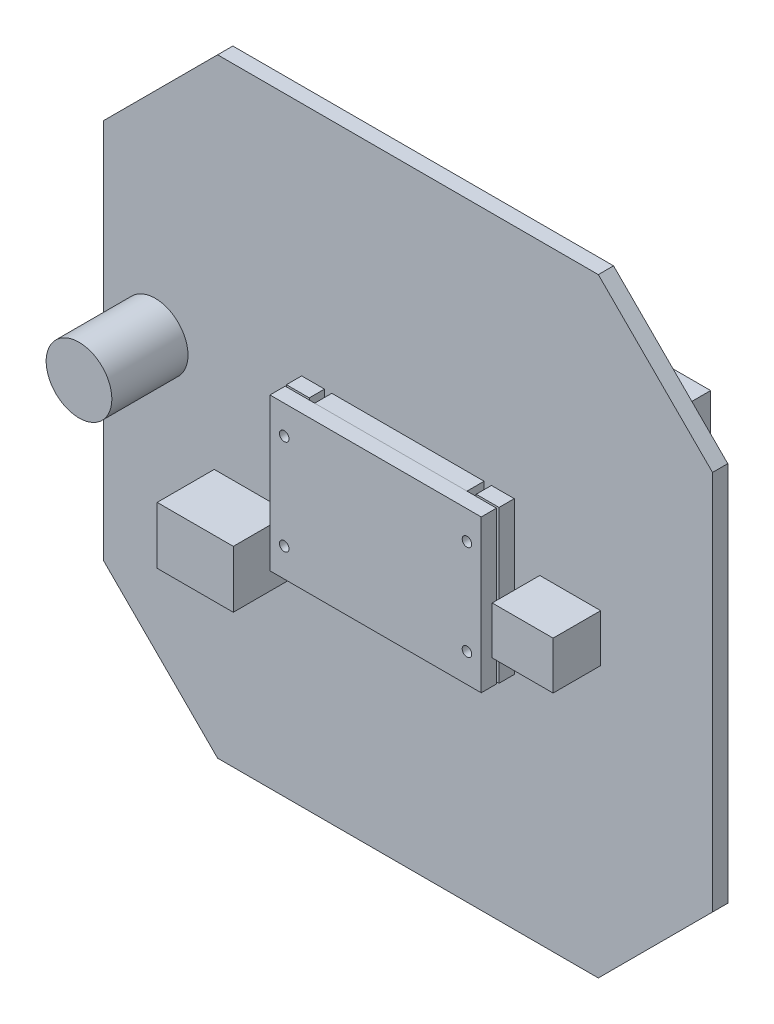
SolidWorks part; units mm, degrees
ref_plane "Front Plane" through (0, 0, 0) normal (0, 0, 1) x (1, 0, 0)
ref_plane "Top Plane" through (0, 0, 0) normal (0, 1, 0) x (1, 0, 0)
ref_plane "Right Plane" through (0, 0, 0) normal (1, 0, 0) x (0, 0, -1)
ref_plane "Plane1" through (0, -0.4, 0) normal (0, 1, 0) x (1, 0, 0)
ref_axis "FPGA Center" through (0, -0.4, 56.35) along (0, 0, -1)
ref_axis "Board Center" through (0, 0, -2.335) along (0, 0, 1)
sketch "Sketch1" plane through (0, 0, 0) normal (0, 0, 1) x (1, 0, 0)
  line L0 (-10, 16) -> (-16, 10)
  line L1 (-10, 16) -> (10, 16)
  line L2 (-16, 10) -> (-16, -10)
  line L3 (-10, -16) -> (10, -16)
  line L4 (16, 10) -> (16, -10)
  line L5 (-16, 16) -> (16, -16) construction
  line L6 (-16, -16) -> (16, 16) construction
  line L7 (10, 16) -> (16, 10)
  line L8 (16, -10) -> (10, -16)
  line L9 (-16, -10) -> (-10, -16)
  circle A0 centre (0, 0) radius 20 construction
  dimension "D1" = 40
  dimension "D2" = 32
  dimension "D3" = 32
extrude "Boss-Extrude1" add sketch "Sketch1" along normal blind 0.8
sketch "Sketch2" plane through (0, 0, 0) normal (0, 0, -1) x (-1, 0, 0)
  line L1 (5.2243, -14) -> (-11.7757, -14)
  line L2 (5.2243, -14) -> (5.2243, -11)
  line L3 (5.2243, -11) -> (-11.7757, -11)
  line L4 (-11.7757, -14) -> (-11.7757, -11)
  dimension "D1" = 3
  dimension "D2" = 17
  dimension "D3" = 11
  dimension "D4" = 5.2243
extrude "Boss-Extrude2" add sketch "Sketch2" along normal blind 1.5
sketch "Sketch3" plane through (0, 0, 0.8) normal (0, 0, 1) x (1, 0, 0)
  line L1 (-4, 3.6) -> (4, 3.6)
  line L2 (-4, 3.6) -> (-4, -4.4)
  line L3 (-4, -4.4) -> (4, -4.4)
  line L4 (4, 3.6) -> (4, -4.4)
  line L5 (-4, 3.6) -> (4, -4.4) construction
  line L6 (-4, -4.4) -> (4, 3.6) construction
  point P0 (3.0251, -6.0236)
  point P9 (0, -0.4)
  dimension "D1" = 8
  dimension "D2" = 8
extrude "Boss-Extrude3" add sketch "Sketch3" along normal blind 0.9
pattern_circular "CirPattern2" count 4 over 360 about axis through (0, -0.4, 56.35) along (0, 0, -1) of "Boss-Extrude2"
sketch "Sketch5" plane through (0, 0, 0.8) normal (0, 0, 1) x (1, 0, 0)
  line L1 (4.384, -4.4) -> (5.584, -4.4)
  line L2 (4.384, -4.4) -> (4.384, 3.6)
  line L3 (4.384, 3.6) -> (5.584, 3.6)
  line L4 (5.584, -4.4) -> (5.584, 3.6)
  line L5 (4.384, -4.4) -> (5.584, 3.6) construction
  line L6 (4.384, 3.6) -> (5.584, -4.4) construction
  point P0 (4.984, -0.4)
  dimension "D1" = 5
  dimension "D2" = 1.2
  dimension "D3" = 8
extrude "Boss-Extrude4" add sketch "Sketch5" along normal blind 0.8
mirror "Mirror1" about plane through (0, 0, 0) normal (1, 0, 0) of "Boss-Extrude4"
sketch "Sketch6" plane through (0, 0, 1.7) normal (0, 0, 1) x (1, 0, 0)
  line L1 (-5.55, 3.6) -> (5.55, 3.6)
  line L2 (-5.55, 3.6) -> (-5.55, -4.4)
  line L3 (-5.55, -4.4) -> (5.55, -4.4)
  line L4 (5.55, 3.6) -> (5.55, -4.4)
  line L5 (-5.55, 3.6) -> (5.55, -4.4) construction
  line L6 (-5.55, -4.4) -> (5.55, 3.6) construction
  point P0 (0, -0.4)
  dimension "D1" = 11.1
  dimension "D2" = 8
extrude "Boss-Extrude5" add sketch "Sketch6" along normal blind 0.8 separate body
sketch "Sketch10" plane through (0, 0, 0.8) normal (0, 0, 1) x (1, 0, 0)
  line L1 (6.925, 0.775) -> (10.125, 0.775)
  line L2 (6.925, 0.775) -> (6.925, -1.725)
  line L3 (6.925, -1.725) -> (10.125, -1.725)
  line L4 (10.125, 0.775) -> (10.125, -1.725)
  line L5 (6.925, 0.775) -> (10.125, -1.725) construction
  line L6 (6.925, -1.725) -> (10.125, 0.775) construction
  point P0 (8.525, -0.475)
  dimension "D1" = 3.2
  dimension "D2" = 2.5
  dimension "D3" = 8.525
  dimension "D4" = 0.475
extrude "Boss-Extrude7" add sketch "Sketch10" along normal blind 2.5
sketch "Sketch11" plane through (0, 0, 0.8) normal (0, 0, 1) x (1, 0, 0)
  line L1 (-10.175, -2.95) -> (-6.175, -2.95)
  line L2 (-10.175, -2.95) -> (-10.175, -5.95)
  line L3 (-10.175, -5.95) -> (-6.175, -5.95)
  line L4 (-6.175, -2.95) -> (-6.175, -5.95)
  line L5 (-10.175, -2.95) -> (-6.175, -5.95) construction
  line L6 (-10.175, -5.95) -> (-6.175, -2.95) construction
  point P0 (-8.175, -4.45)
  dimension "D1" = 3
  dimension "D2" = 4
  dimension "D3" = 8.175
  dimension "D4" = 4.05
extrude "Boss-Extrude8" add sketch "Sketch11" along normal blind 3
sketch "Sketch12" plane through (0, 0, 0.8) normal (0, 0, 1) x (1, 0, 0)
  circle A0 centre (-13.28, 1.56) radius 1.725
  dimension "D3" = 3.45
  dimension "D1" = 13.28
  dimension "D2" = 1.96
extrude "Boss-Extrude10" add sketch "Sketch12" along normal blind 4
ref_plane "Plane2" through (-5.55, -4.4, 2.5) normal (0, -1, 0) x (-1, 0, 0)
sketch "Sketch14" plane through (0, 0, 2.5) normal (0, 0, 1) x (1, 0, 0)
  line L0 (-5.55, -4.4) -> (5.55, -4.4) construction
  line L1 (-5.55, 3.6) -> (-5.55, -4.4) construction
  line L2 (5.55, 3.6) -> (-5.55, 3.6) construction
  circle A0 centre (-4.8, 2.1) radius 0.25
  circle A1 centre (-4.8, -2.9) radius 0.25
  dimension "D1" = 0.5
  dimension "D2" = 0.5
  dimension "D3" = 1.5
  dimension "D4" = 0.75
  dimension "D5" = 0.75
  dimension "D6" = 1.5
extrude "Cut-Extrude1" cut sketch "Sketch14" against normal up to next (0.8 mm away)
mirror "Mirror2" about plane through (0, 0, 0) normal (1, 0, 0) of "Cut-Extrude1"
